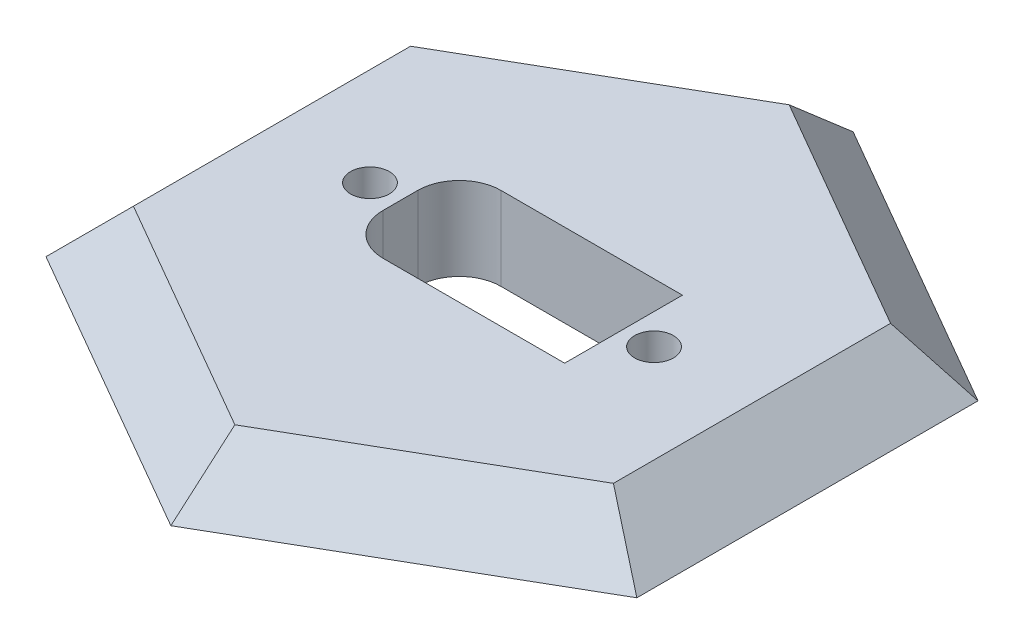
SolidWorks part; units mm, degrees
ref_plane "Płaszczyzna przednia" through (0, 0, 0) normal (0, 0, 1) x (1, 0, 0)
ref_plane "Płaszczyzna górna" through (0, 0, 0) normal (0, 1, 0) x (1, 0, 0)
ref_plane "Płaszczyzna prawa" through (0, 0, 0) normal (1, 0, 0) x (0, 0, -1)
sketch "Sketch1" plane through (0, 0, 0) normal (0, 1, 0) x (1, 0, 0)
  circle A0 centre (0, 0) radius 26
extrude "Boss-Extrude1" add sketch "Sketch1" along normal blind 4
sketch "Sketch3" plane through (0, 0, 0) normal (0, -1, 0) x (1, 0, 0)
  circle A0 centre (0, 0) radius 15
extrude "Boss-Extrude2" add sketch "Sketch3" along normal blind 2
sketch "Sketch2" plane through (0, 4, 0) normal (0, 1, 0) x (1, 0, 0)
  line L1 (-5.05, -4.25) -> (8.05, -4.25)
  line L2 (-8.05, -1.25) -> (-8.05, 1.25)
  line L3 (-5.05, 4.25) -> (8.05, 4.25)
  line L4 (8.05, -4.25) -> (8.05, 4.25)
  line L5 (-8.05, -4.25) -> (8.05, 4.25) construction
  line L6 (-8.05, 4.25) -> (8.05, -4.25) construction
  arc A0 (-5.05, -4.25) -> (-8.05, -1.25) centre (-5.05, -1.25) cw
  arc A1 (-8.05, 1.25) -> (-5.05, 4.25) centre (-5.05, 1.25) cw
  point P0 (0, 0)
  dimension "D3" = 3
  dimension "D1" = 8.5
  dimension "D2" = 16.1
extrude "Cut-Extrude1" cut sketch "Sketch2" against normal blind 20
sketch "Sketch4" plane through (0, 4, 0) normal (0, 1, 0) x (1, 0, 0)
  line L0 (0, 0) -> (-10.25, 0) construction
  line L1 (0, 0) -> (10.25, 0) construction
  circle A0 centre (-10.25, 0) radius 1.4
  circle A1 centre (10.25, 0) radius 1.4
extrude "Cut-Extrude2" cut sketch "Sketch4" against normal blind 10
sketch "Sketch6" plane through (0, 4, 0) normal (0, 1, 0) x (1, 0, 0)
  line L1 (0, 20) -> (-17.3205, 10)
  line L2 (-17.3205, 10) -> (-17.3205, -10)
  line L3 (-17.3205, -10) -> (0, -20)
  line L4 (0, -20) -> (17.3205, -10)
  line L5 (17.3205, -10) -> (17.3205, 10)
  line L6 (17.3205, 10) -> (0, 20)
  circle A0 centre (0, 0) radius 20 construction
  circle A1 centre (0, 0) radius 17.3205 construction
  point P3 (0, 18)
extrude "Cut-Extrude3" cut sketch "Sketch6" against normal blind 10 draft 45 flip side to cut
